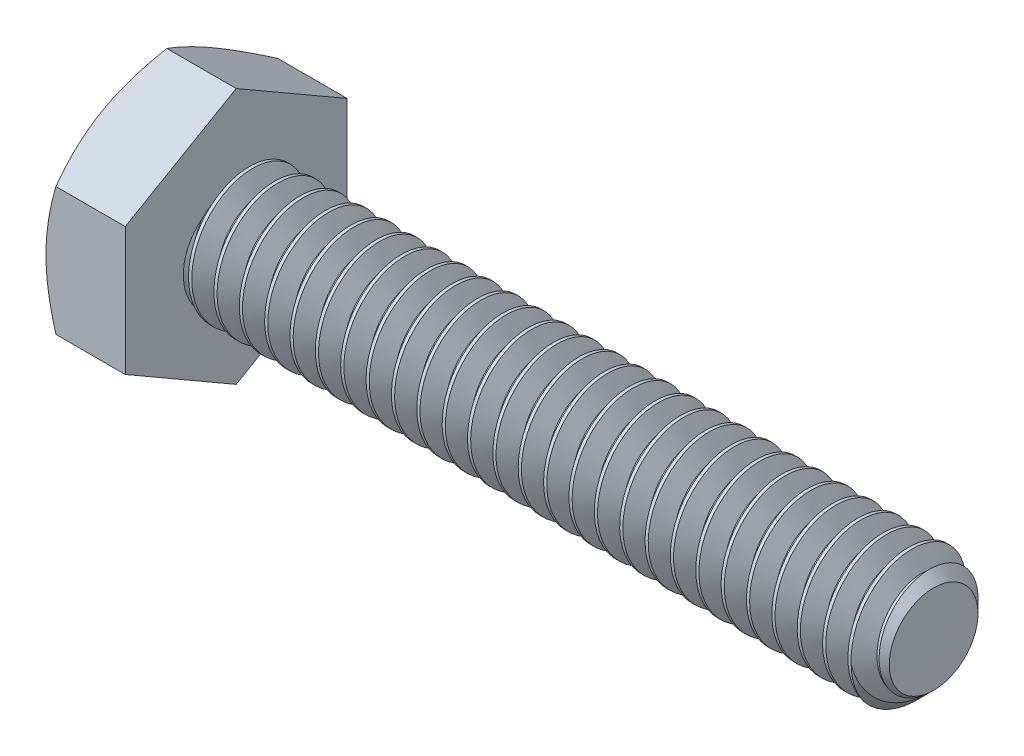
SolidWorks part; units mm, degrees
material "Stainless Steel 304"
ref_plane "Front Plane" through (0, 0, 0) normal (0, 0, 1) x (1, 0, 0)
ref_plane "Top Plane" through (0, 0, 0) normal (0, 1, 0) x (1, 0, 0)
ref_plane "Right Plane" through (0, 0, 0) normal (1, 0, 0) x (0, 0, -1)
sketch "Sketch1" plane through (0, 0, 0) normal (0, 0, 1) x (1, 0, 0)
  line L0 (-19.4469, 0) -> (19.4469, 0) construction
  line L1 (19.4469, 3.175) -> (19.4469, -3.175) construction
  line L2 (-15.4781, 5.5562) -> (-15.4781, -5.5562) construction
  line L3 (-19.4469, 5.5562) -> (-19.4469, -5.5562) construction
  point P9 (-15.4781, 0)
  point P10 (15.0019, -3.175)
  dimension "Screw Dia" = 6.35
  dimension "Hex" = 11.1125
  dimension "Head Ht" = 3.9688
  dimension "Screw Lenght" = 34.925
  dimension "D1" = 4.445
ref_plane "Plane2" through (19.4469, 0, 0) normal (1, 0, 0) x (0, 0, -1)
sketch "Sketch5" plane through (19.4469, 0, 0) normal (1, 0, 0) x (0, 0, -1)
  circle A0 centre (0, 0) radius 3.175
extrude "Boss-Extrude3" add sketch "Sketch5" against normal up to vertex (34.925 mm away) up to point (-15.4781, 0, 0)
sketch "Sketch9" plane through (19.4469, 0, 0) normal (1, 0, 0) x (0, 0, -1)
  circle A1 centre (0, 0) radius 3.175
  circle A2 centre (0, 0) radius 3.175
  dimension "D1" = 0
curve "Helix/Spiral1" pitch 1.27 height 36.195 turns 28.5 parameters "Pitch"=1.27
chamfer "Chamfer1" distance 0.9525 angle 45 1 edges at (19.4469, 0, -3.175)
sketch "Sketch10" plane through (0, 0, 0) normal (0, 0, 1) x (1, 0, 0)
  line L0 (19.4469, 3.175) -> (19.9231, 2.3501)
  line L1 (19.9231, 2.3501) -> (20.0819, 2.3501)
  line L2 (20.0819, 2.3501) -> (20.5581, 3.175)
  line L3 (19.4469, 3.175) -> (20.5581, 3.175)
  line L4 (20.0025, 3.175) -> (20.0025, 2.3501) construction
  line L5 (19.685, 2.7626) -> (20.32, 2.7626) construction
  dimension "D1" = 60
  dimension "D2" = 0.1588
  dimension "D3" = 0.635
sweep "Cut-Sweep1" cut profiles "Sketch10" path "Helix/Spiral1" align with end faces yes
sketch "Sketch6" plane through (-15.4781, 0, 0) normal (-1, 0, 0) x (0, 0, 1)
  line L0 (0, 5.5562) -> (0, -5.5562) construction
  line L1 (5.5562, 3.2079) -> (0, 6.4158)
  line L2 (0, 6.4158) -> (-5.5562, 3.2079)
  line L3 (-5.5562, 3.2079) -> (-5.5562, -3.2079)
  line L4 (-5.5562, -3.2079) -> (0, -6.4158)
  line L5 (0, -6.4158) -> (5.5562, -3.2079)
  line L6 (5.5562, -3.2079) -> (5.5562, 3.2079)
  circle A0 centre (0, 0) radius 5.5562 construction
extrude "Boss-Extrude4" add sketch "Sketch6" along normal up to vertex (3.9688 mm away) up to point (-19.4469, -5.5562, 0)
sketch "Sketch7" plane through (-19.4469, 0, 0) normal (-1, 0, 0) x (0, 0, 1)
  circle A0 centre (0, 0) radius 5.5562 construction
  circle A1 centre (0, 0) radius 5.5562
sketch "Sketch8" plane through (-19.4469, 0, 0) normal (-1, 0, 0) x (0, 0, 1)
  circle A0 centre (0, 0) radius 5.5562 construction
  circle A1 centre (0, 0) radius 5.5562
extrude "Cut-Extrude3" cut sketch "Sketch8" against normal through all draft 60 flip side to cut
equation "\"D2@Sketch10\" = \"Pitch@Helix/Spiral1\"*.125"
equation "\"D3@Sketch10\" = \"Pitch@Helix/Spiral1\"*.5"
equation "\"D3@Helix/Spiral1\" = \"Screw Lenght@Sketch1\"+\"Pitch@Helix/Spiral1\""
equation "\"D1@Chamfer1\" = \"Pitch@Helix/Spiral1\"*.75"
equation "\"D1@Sketch1\" = \"Pitch@Helix/Spiral1\"*3.5"
